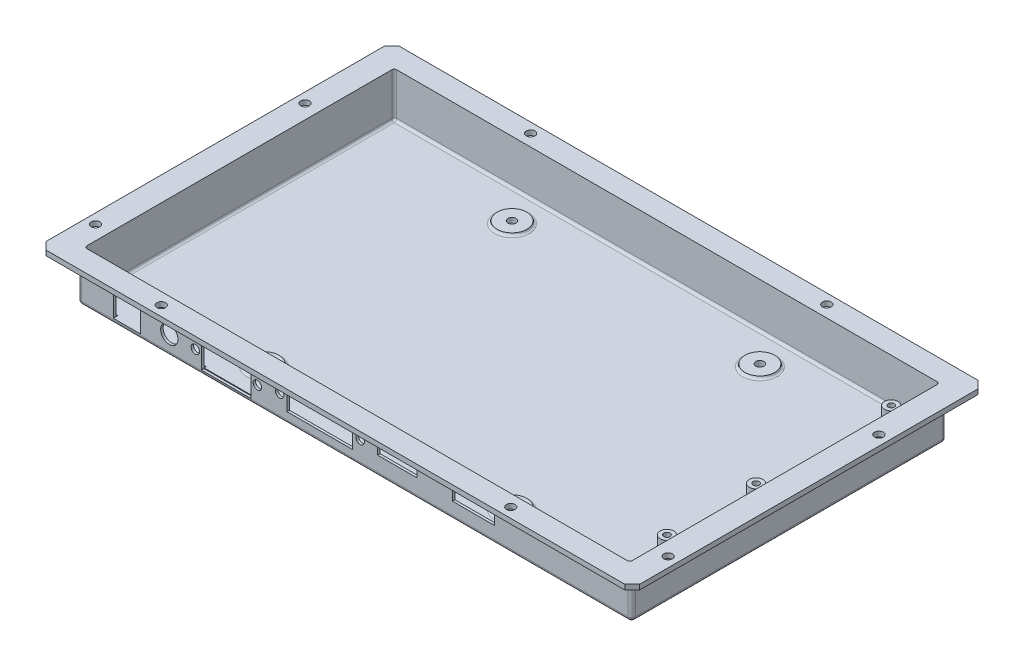
SolidWorks part; units mm, degrees
ref_plane "Front Plane" through (0, 0, 0) normal (0, 0, 1) x (1, 0, 0)
ref_plane "Top Plane" through (0, 0, 0) normal (0, 1, 0) x (1, 0, 0)
ref_plane "Right Plane" through (0, 0, 0) normal (1, 0, 0) x (0, 0, -1)
sketch "Sketch1" plane through (0, 0, 0) normal (0, 1, 0) x (1, 0, 0)
  line L1 (0, 0) -> (239.5, 0)
  line L2 (0, 0) -> (0, 142.5)
  line L3 (0, 142.5) -> (239.5, 142.5)
  line L4 (239.5, 0) -> (239.5, 142.5)
  dimension "D1" = 142.5
  dimension "D2" = 239.5
extrude "Boss-Extrude1" add sketch "Sketch1" along normal blind 20
sketch "Sketch2" plane through (0, 0, 0) normal (0, -1, 0) x (1, 0, 0)
  line L0 (119.75, 0) -> (119.75, 21.064) construction
  line L1 (8, -7.75) -> (231.5, -7.75)
  line L2 (8, -7.75) -> (8, -134.75)
  line L3 (8, -134.75) -> (231.5, -134.75)
  line L4 (231.5, -7.75) -> (231.5, -134.75)
  line L5 (0, 0) -> (239.5, 0) construction
  line L6 (0, -71.25) -> (-26.2739, -71.25) construction
  line L7 (0, -142.5) -> (0, 0) construction
  dimension "D1" = 223.5
  dimension "D2" = 127
extrude "Cut-Extrude1" cut sketch "Sketch2" against normal blind 18 flip side to cut contours L2 L3 L4 L1
sketch "Sketch3" plane through (0, 20, 0) normal (0, 1, 0) x (1, 0, 0)
  line L0 (119.75, 142.5) -> (119.75, 159.2388) construction
  line L1 (9.75, 133.75) -> (229.75, 133.75)
  line L2 (9.75, 133.75) -> (9.75, 8.75)
  line L3 (9.75, 8.75) -> (229.75, 8.75)
  line L4 (229.75, 133.75) -> (229.75, 8.75)
  line L5 (239.5, 142.5) -> (0, 142.5) construction
  line L6 (0, 71.25) -> (-15.5355, 71.25) construction
  line L7 (0, 142.5) -> (0, 0) construction
  dimension "D1" = 220
  dimension "D2" = 125
extrude "Cut-Extrude2" cut sketch "Sketch3" against normal blind 18
sketch "Sketch4" plane through (0, 2, 0) normal (0, 1, 0) x (1, 0, 0)
  line L0 (229.75, 8.75) -> (229.75, 133.75) construction
  line L2 (9.75, 8.75) -> (229.75, 8.75) construction
  circle A0 centre (214.75, 129.25) radius 2.75
  circle A1 centre (214.75, 74.75) radius 2.75
  circle A2 centre (214.75, 38.75) radius 2.75
  dimension "D1" = 5.5
  dimension "D2" = 54.5
  dimension "D3" = 36
  dimension "D4" = 15
  dimension "D6" = 30
extrude "Boss-Extrude3" add sketch "Sketch4" along normal blind 5
sketch "Sketch5" plane through (0, 7, 0) normal (0, 1, 0) x (1, 0, 0)
  circle A0 centre (214.75, 129.25) radius 1.25
  circle A1 centre (214.75, 74.75) radius 1.25
  circle A2 centre (214.75, 38.75) radius 1.25
  dimension "D1" = 2.5
extrude "Cut-Extrude3" cut sketch "Sketch5" against normal blind 6
sketch "Sketch6" plane through (0, 2, 0) normal (0, 1, 0) x (1, 0, 0)
  line L0 (214.75, 129.25) -> (214.75, 135.5986) construction
  line L1 (229.75, 8.75) -> (229.75, 133.75) construction
  circle A0 centre (214.75, 129.25) radius 2.75 construction
  circle A2 centre (214.85, 92.6501) radius 2.75
  circle A3 centre (214.85, 82.6501) radius 2.75
  circle A4 centre (214.85, 66.6501) radius 2.75
  circle A5 centre (214.85, 56.6501) radius 2.75
  circle A6 centre (214.85, 46.6501) radius 2.75
  dimension "D1" = 36.6
  dimension "D2" = 14.9
  dimension "D6" = 10
  dimension "D7" = 16
  dimension "D8" = 10
  dimension "D9" = 10
  dimension "D3" = 5.5
extrude "Cut-Extrude4" cut sketch "Sketch6" against normal through all
sketch "Sketch7" plane through (0, 18, 0) normal (0, -1, 0) x (1, 0, 0)
  line L0 (0, -142.5) -> (239.5, -142.5) construction
  line L1 (239.5, -142.5) -> (239.5, 0) construction
  line L2 (0, 0) -> (0, -142.5) construction
  line L3 (239.5, 0) -> (0, 0) construction
  circle A0 centre (179.5, -138.5) radius 1.75
  circle A1 centre (60, -138.5) radius 1.75
  circle A2 centre (235.5, -103.5) radius 1.75
  circle A3 centre (235.5, -18.5) radius 1.75
  circle A4 centre (186.5, -4) radius 1.75
  circle A5 centre (45.5, -4) radius 1.75
  circle A6 centre (4, -19) radius 1.75
  circle A7 centre (4, -103.5) radius 1.75
  dimension "D1" = 3.5
  dimension "D2" = 4
  dimension "D3" = 4
  dimension "D4" = 39
  dimension "D5" = 4
  dimension "D6" = 19
  dimension "D7" = 53
  dimension "D9" = 60
  dimension "D10" = 45.5
  dimension "D11" = 4
  dimension "D12" = 85
  dimension "D8" = 60
extrude "Cut-Extrude5" cut sketch "Sketch7" against normal through all
sketch "Sketch8" plane through (0, 0, -7.75) normal (0, 0, 1) x (1, 0, 0)
  line L0 (231.5, 18) -> (231.5, 0) construction
  line L1 (176.2, 6.5) -> (159.2, 6.5)
  line L2 (176.2, 6.5) -> (176.2, 13)
  line L3 (176.2, 13) -> (159.2, 13)
  line L4 (159.2, 6.5) -> (159.2, 13)
  line L5 (145, 7.5) -> (129, 7.5)
  line L6 (145, 7.5) -> (145, 14.5)
  line L7 (145, 14.5) -> (129, 14.5)
  line L8 (129, 7.5) -> (129, 14.5)
  line L9 (119, 4.4) -> (92.5, 4.4)
  line L10 (119, 4.4) -> (119, 14.4)
  line L11 (119, 14.4) -> (92.5, 14.4)
  line L12 (92.5, 4.4) -> (92.5, 14.4)
  line L13 (78, 1.7) -> (58, 1.7)
  line L14 (78, 1.7) -> (78, 13.7)
  line L15 (78, 13.7) -> (58, 13.7)
  line L16 (58, 1.7) -> (58, 13.7)
  line L19 (33.4, 15) -> (22.4, 15)
  line L21 (33.4, 2) -> (22.4, 2)
  line L22 (33.4, 2) -> (33.4, 15)
  line L23 (167.7, 6.5) -> (167.7, 1.4506) construction
  line L24 (22.4, 2) -> (22.4, 15)
  line L27 (0, 20) -> (239.5, 20) construction
  line L28 (8, 18) -> (8, 0) construction
  line L30 (105.75, 4.4) -> (105.75, -3.0494) construction
  line L31 (68, 1.7) -> (68, -2.5736) construction
  line L32 (176.2, 9.75) -> (173.3268, 9.75) construction
  line L33 (119, 9.4) -> (114.4987, 9.4) construction
  line L34 (78, 7.7) -> (73.9638, 7.7) construction
  circle A0 centre (55.5, 7.7) radius 1.7
  circle A1 centre (80.5, 7.7) radius 1.7
  circle A2 centre (45, 7.65) radius 3.5
  circle A3 centre (89.5, 9.4) radius 1.7
  circle A4 centre (122, 9.4) radius 1.7
  point P28 (231.5, 9)
  dimension "D25" = 7
  dimension "D26" = 37
  dimension "D27" = 12.35
  dimension "D28" = 25
  dimension "D29" = 32.5
  dimension "D1" = 17
  dimension "D2" = 6.5
  dimension "D3" = 55.3
  dimension "D4" = 7
  dimension "D5" = 16
  dimension "D6" = 7
  dimension "D7" = 86.5
  dimension "D8" = 5.5
  dimension "D9" = 26.5
  dimension "D10" = 10
  dimension "D11" = 112.5
  dimension "D12" = 5.6
  dimension "D13" = 20
  dimension "D14" = 12
  dimension "D15" = 6.3
  dimension "D16" = 50
  dimension "D17" = 11
  dimension "D18" = 14.4
  dimension "D19" = 13
  dimension "D23" = 5
extrude "Cut-Extrude6" cut sketch "Sketch8" against normal up to surface (1 mm away) up to face at (119.75, 11, -8.75)
chamfer "Chamfer1" distance 3 angle 45 4 edges at (239.5, 19, -142.5) (0, 19, -142.5) (0, 19, 0) (239.5, 19, 0)
sketch "Sketch9" plane through (0, 0, 0) normal (0, -1, 0) x (1, 0, 0)
  line L0 (9.75, -71.25) -> (-14.6092, -71.25) construction
  line L1 (9.75, -133.75) -> (9.75, -8.75) construction
  line L2 (119.75, -142.5) -> (119.75, -161.8741) construction
  line L3 (236.5, -142.5) -> (3, -142.5) construction
  circle A0 centre (69.75, -121.25) radius 6
  circle A1 centre (169.75, -121.25) radius 6
  circle A2 centre (69.75, -21.25) radius 6
  circle A3 centre (169.75, -21.25) radius 6
  dimension "D3" = 12
  dimension "D1" = 100
  dimension "D2" = 100
extrude "Boss-Extrude4" add sketch "Sketch9" along normal blind 5 and the other way blind 3
sketch "Sketch10" plane through (0, -5, 0) normal (0, -1, 0) x (1, 0, 0)
  circle A0 centre (69.75, -121.25) radius 1.65
  circle A1 centre (169.75, -121.25) radius 1.65
  circle A2 centre (169.75, -21.25) radius 1.65
  circle A3 centre (69.75, -21.25) radius 1.65
  dimension "D1" = 3.3
extrude "Cut-Extrude7" cut sketch "Sketch10" against normal through all
fillet "Fillet1" radius 2 4 edges at (169.75, 0, -127.25) (69.75, 0, -127.25) (69.75, 0, -27.25) (169.75, 0, -27.25)
fillet "Fillet2" radius 1 10 edges at (9.75, 11, -133.75) (9.75, 11, -8.75) (9.75, 2, -71.25) (16.075, 2, -8.75) (45.7, 2, -8.75) (153.875, 2, -8.75) (229.75, 11, -8.75) (119.75, 2, -133.75) (229.75, 2, -71.25) (229.75, 11, -133.75)
fillet "Fillet3" radius 1.5 8 edges at (8, 9, -7.75) (231.5, 9, -7.75) (231.5, 9, -134.75) (231.5, 0, -71.25) (119.75, 0, -134.75) (119.75, 0, -7.75) (8, 0, -71.25) (8, 9, -134.75)
fillet "Fillet4" radius 1 4 edges at (169.75, 2, -115.25) (69.75, 2, -115.25) (169.75, 2, -15.25) (69.75, 2, -15.25)
